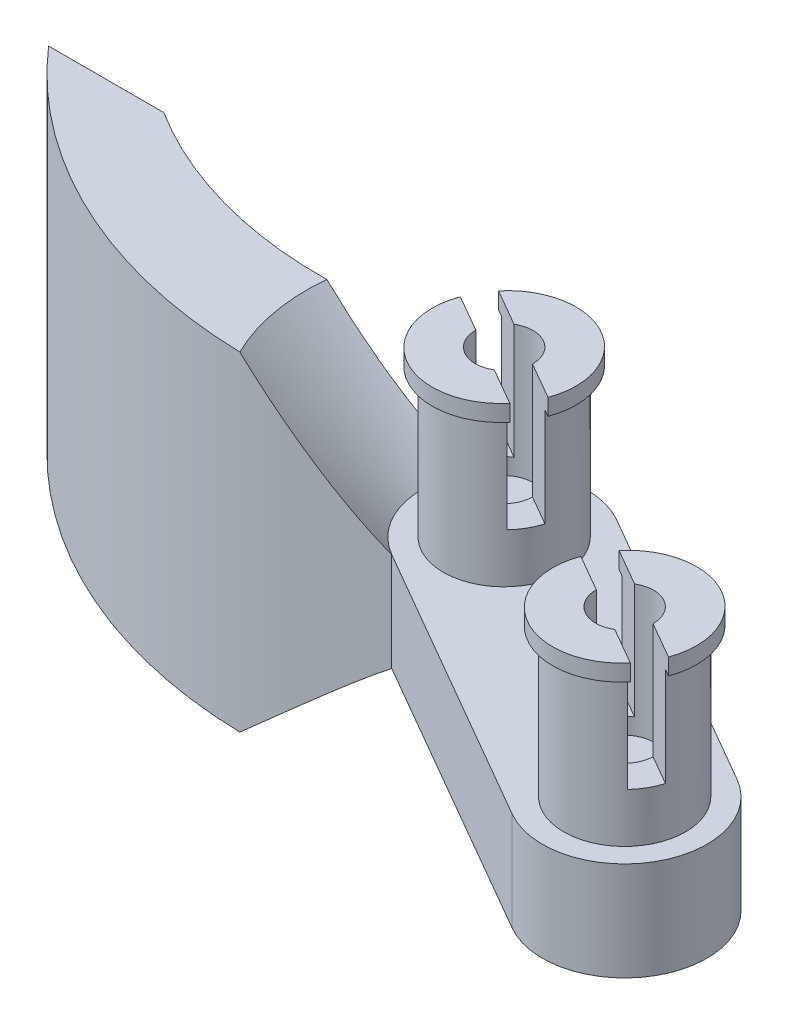
SolidWorks part; units mm, degrees
ref_plane "Front Plane" through (0, 0, 0) normal (0, 0, 1) x (1, 0, 0)
ref_plane "Top Plane" through (0, 0, 0) normal (0, 1, 0) x (1, 0, 0)
ref_plane "Right Plane" through (0, 0, 0) normal (1, 0, 0) x (0, 0, -1)
sketch "Sketch1" plane through (0, 0, 0) normal (0, 1, 0) x (1, 0, 0)
  line L0 (-19.8205, 5.6699) -> (-2.5, -4.3301)
  line L1 (2.5, 4.3301) -> (-14.8205, 14.3301)
  line L2 (-17.3205, 15) -> (-43, 15) construction
  line L3 (-43, 15) -> (-50, 15)
  line L4 (0, 0) -> (-21.6506, 12.5) construction
  line L5 (-19.8205, 5.6699) -> (-14.8205, 14.3301) construction
  line L6 (0, -5) -> (-15.3949, -5) construction
  line L7 (0, 0) -> (2.5, 4.3301) construction
  circle A0 centre (0, 0) radius 3.7
  circle A1 centre (0, 0) radius 5
  arc A2 (-43, 15) -> (-21.6506, 12.5) centre (-29.7001, 36.1687) ccw
  arc A3 (-14.8205, 14.3301) -> (-14.9376, 14.3957) centre (-7.2881, 27.928) cw
  circle A4 centre (0, 0) radius 1.75
  circle A5 centre (-17.3205, 10) radius 5
  circle A6 centre (-17.3205, 10) radius 3.7
  circle A7 centre (-17.3205, 10) radius 1.75
  arc A8 (-50, 15) -> (-19.8205, 5.6699) centre (-27.3769, 34.7026) ccw
  point P19 (0, 5.2379)
  dimension "D1" = 7.4
  dimension "D2" = 10
  dimension "D7" = 3.5
  dimension "D8" = 30
  dimension "D6" = 25
  dimension "D4" = 7
  dimension "D5" = 50
  dimension "D10" = 30
  dimension "D9" = 10
extrude "Boss-Extrude1" add sketch "Sketch1" along normal blind 6 contours A1 L1 | A1 A0 | A0 A4 | A4 | A1 L1 L5 | A6 L5 A5 | A7 L5 A6 | L5 A7 | A7 L5 A6 | L5 A7 region at (-8.6603, 0, -5) region at (-22.0135, 0, -8.7425) region at (-4.2077, 0, -2.4293) region at (-3.5953, 0, 0) region at (0, 0, 0) region at (-20.9159, 0, -10) region at (-17.3205, 0, -10)
extrude "Boss-Extrude2" add sketch "Sketch1<4>" along normal blind 13 and the other way blind 7 contours L3 A8 A5 A2 region at (-33.9332, 0, -9.441)
sketch "Sketch1<4>" plane through (0, 0, 0) normal (0, 1, 0) x (1, 0, 0) same geometry as "Sketch1"
extrude "Boss-Extrude3" add sketch "Sketch1<5>" along normal blind 15 contours A0 A4 | A7 L5 A6 | A7 L5 A6 region at (-3.5953, 0, 0) region at (-20.9159, 0, -10)
sketch "Sketch1<5>" plane through (0, 0, 0) normal (0, 1, 0) x (1, 0, 0) same geometry as "Sketch1"
chamfer "Chamfer2" distance 7 angle 45 2 edges at (-22.1501, -7, -8.7059) (-22.1501, 13, -8.7059)
sketch "Sketch3" plane through (0, 15, 0) normal (0, 1, 0) x (1, 0, 0)
  line L0 (-6.1603, 9.3301) -> (-11.1603, 0.6699) construction
  line L1 (2.5, 4.3301) -> (-14.8205, 14.3301) construction
  line L2 (-19.8205, 5.6699) -> (-2.5, -4.3301) construction
  line L3 (4.3301, -2.5) -> (-21.6506, 12.5) construction
  line L4 (-20.0141, 12.5366) -> (-18.2203, 11.501)
  line L5 (-19.1705, 6.7957) -> (-15.4705, 13.2043) construction
  line L6 (-13.7769, 8.9356) -> (-15.5707, 9.9713)
  line L7 (-14.6269, 7.4634) -> (-16.4207, 8.499)
  line L8 (-20.8641, 11.0644) -> (-19.0703, 10.0287)
  line L9 (-1.85, -3.2043) -> (1.85, 3.2043) construction
  line L10 (2.6936, -2.5366) -> (0.8998, -1.501)
  line L11 (-3.5436, 1.0644) -> (-1.7498, 0.0287)
  line L12 (-2.6936, 2.5366) -> (-0.8998, 1.501)
  line L13 (3.5436, -1.0644) -> (1.7498, -0.0287)
  arc A0 (-2.5, -4.3301) -> (2.5, 4.3301) centre (0, 0) ccw construction
  circle A1 centre (-17.3205, 10) radius 3.7 construction
  circle A2 centre (-17.3205, 10) radius 1.75 construction
  circle A5 centre (-17.3205, 10) radius 1.75 construction
  circle A6 centre (-17.3205, 10) radius 3.7 construction
  arc A7 (-20.8641, 11.0644) -> (-20.0141, 12.5366) centre (-17.3205, 10) cw
  arc A8 (-19.0703, 10.0287) -> (-18.2203, 11.501) centre (-17.3205, 10) cw
  arc A9 (-16.4207, 8.499) -> (-15.5707, 9.9713) centre (-17.3205, 10) ccw
  arc A10 (-14.6269, 7.4634) -> (-13.7769, 8.9356) centre (-17.3205, 10) ccw
  circle A11 centre (0, 0) radius 1.75 construction
  arc A12 (-3.5436, 1.0644) -> (-2.6936, 2.5366) centre (0, 0) cw
  arc A13 (-1.7498, 0.0287) -> (-0.8998, 1.501) centre (0, 0) cw
  arc A14 (0.8998, -1.501) -> (1.7498, -0.0287) centre (0, 0) ccw
  arc A15 (2.6936, -2.5366) -> (3.5436, -1.0644) centre (0, 0) ccw
  dimension "D1" = 0.85
extrude "Cut-Extrude1" cut sketch "Sketch3" against normal blind 6
sketch "Sketch4" plane through (0, 6, 0) normal (0, 1, 0) x (1, 0, 0)
  line L0 (-11.1603, 0.6699) -> (-6.1603, 9.3301) construction
  line L1 (-19.8205, 5.6699) -> (-2.5, -4.3301) construction
  line L2 (2.5, 4.3301) -> (-14.8205, 14.3301) construction
  circle A0 centre (-17.3205, 10) radius 1.75
  circle A1 centre (0, 0) radius 1.75
extrude "Boss-Extrude5" add sketch "Sketch4" along normal blind 2
sketch "Sketch6" plane through (0, 15, 0) normal (0, 1, 0) x (1, 0, 0)
  line L0 (-18.2203, 11.501) -> (-20.4471, 12.7866)
  line L1 (-15.5707, 9.9713) -> (-13.3439, 8.6856)
  line L2 (-20.5248, 11.85) -> (-14.1162, 8.15) construction
  line L3 (-16.4207, 8.499) -> (-14.1939, 7.2134)
  line L4 (-19.0703, 10.0287) -> (-21.2971, 11.3144)
  line L5 (-11.1603, 0.6699) -> (-6.1603, 9.3301) construction
  line L6 (-19.8205, 5.6699) -> (-2.5, -4.3301) construction
  line L7 (2.5, 4.3301) -> (-14.8205, 14.3301) construction
  line L8 (3.2043, -1.85) -> (-3.2043, 1.85) construction
  line L9 (0.8998, -1.501) -> (3.1266, -2.7866)
  line L10 (-1.7498, 0.0287) -> (-3.9766, 1.3144)
  line L11 (-0.8998, 1.501) -> (-3.1266, 2.7866)
  line L12 (1.7498, -0.0287) -> (3.9766, -1.3144)
  arc A0 (-20.4471, 12.7866) -> (-13.3439, 8.6856) centre (-17.2415, 10.1369) cw
  arc A2 (-18.2203, 11.501) -> (-15.5707, 9.9713) centre (-17.3205, 10) cw
  circle A3 centre (-17.3205, 10) radius 1.75 construction
  arc A4 (-20.0141, 12.5366) -> (-20.8641, 11.0644) centre (-17.3205, 10) ccw construction
  arc A5 (-14.6269, 7.4634) -> (-13.7769, 8.9356) centre (-17.3205, 10) ccw construction
  arc A6 (-19.0703, 10.0287) -> (-16.4207, 8.499) centre (-17.3205, 10) ccw
  arc A7 (-21.2971, 11.3144) -> (-14.1939, 7.2134) centre (-17.3995, 9.8631) ccw
  arc A8 (3.1266, -2.7866) -> (-3.9766, 1.3144) centre (-0.079, -0.1369) cw
  arc A9 (0.8998, -1.501) -> (-1.7498, 0.0287) centre (0, 0) cw
  arc A10 (1.7498, -0.0287) -> (-0.8998, 1.501) centre (0, 0) ccw
  arc A11 (3.9766, -1.3144) -> (-3.1266, 2.7866) centre (0.079, 0.1369) ccw
  dimension "D2" = 4.159
  dimension "D1" = 0.5
extrude "Boss-Extrude6" add sketch "Sketch6" along normal blind 1
